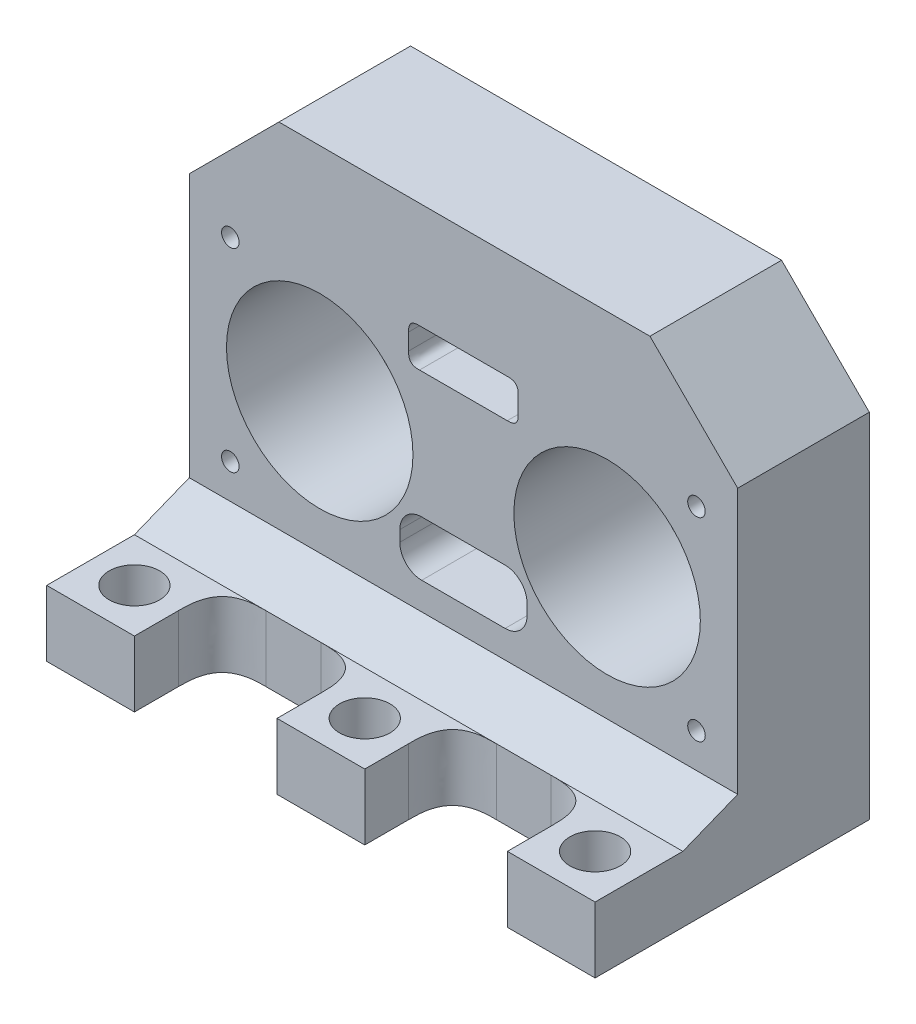
SolidWorks part; units mm, degrees
ref_plane "Plan de face" through (0, 0, 0) normal (0, 0, 1) x (1, 0, 0)
ref_plane "Plan de dessus" through (0, 0, 0) normal (0, 1, 0) x (1, 0, 0)
ref_plane "Plan de droite" through (0, 0, 0) normal (1, 0, 0) x (0, 0, -1)
sketch "Esquisse1" plane through (0, 0, 0) normal (0, 0, 1) x (1, 0, 0)
  line L0 (0, 0) -> (13.1, 0) construction
  line L1 (0, 0) -> (-13.1, 0) construction
  line L2 (0, 0) -> (0, -4.5) construction
  line L14 (0, -4.5) -> (0, -7) construction
  line L15 (0, -7) -> (5.8, -7) construction
  line L16 (5.8, -7) -> (5.8, -4.5)
  line L19 (5.8, -4.5) -> (-5.8, -4.5)
  line L20 (-5.8, -4.5) -> (-5.8, -9.5)
  line L27 (0, 0) -> (-24.9927, 0) construction
  line L28 (-5.8, -9.5) -> (5.8, -9.5)
  line L30 (-24.9927, 12) -> (-16.8203, 20.1724)
  line L31 (-24.9927, 12) -> (-24.9927, 20) construction
  line L32 (25.0073, -20) -> (0.0073, -20)
  line L33 (0.0073, -20) -> (-24.9927, -20)
  line L34 (-24.9927, -20) -> (-24.9927, 0)
  line L35 (25.0073, 20.1724) -> (25.0073, 12.1724) construction
  line L36 (5.8, -9.5) -> (5.8, -7)
  line L37 (-24.9927, 0) -> (-24.9927, 12)
  line L38 (25.0073, 12.1724) -> (25.0073, -20)
  line L39 (25.0073, 20.1724) -> (17.0073, 20.1724) construction
  line L40 (17.0073, 20.1724) -> (25.0073, 12.1724)
  line L41 (-24.9927, 20) -> (-16.8203, 20.1724) construction
  line L44 (-16.8203, 20.1724) -> (17.0073, 20.1724)
  circle A0 centre (-13.1, 0) radius 8.5
  circle A1 centre (13.1, 0) radius 8.5
  dimension "D3" = 5.8
  dimension "D4" = 4.5
  dimension "D2" = 13.1
  dimension "D5" = 2.5
  dimension "D6" = 11.6
  dimension "D7" = 7
  dimension "D8" = 5
  dimension "D11" = 8
  dimension "D12" = 20
  dimension "D13" = 25
  dimension "D14" = 25
  dimension "D16" = 40
  dimension "D17" = 40.1724
extrude "Boss.-Extru.1" add sketch "Esquisse1" along normal blind 12 contours L44 L30 L37 L34 L33 L32 L38 L40 L20 A1 A0 region at (0.0304, -0.3939, 0)
fillet "Congé1" radius 2 4 edges at (5.8, -9.5, 6) (-5.8, -9.5, 6) (5.8, -4.5, 6) (-5.8, -4.5, 6)
sketch "Esquisse2" plane through (0, 0, 0) normal (0, 0, -1) x (-1, 0, 0)
  line L4 (-5.8, -6.5) -> (-3.8, -6.5) construction
  line L5 (-3.8, -6.5) -> (3.8, -6.5) construction
  line L6 (3.8, -6.5) -> (5.8, -6.5) construction
  line L7 (5.8, -6.5) -> (5.8, -7.5) construction
  line L8 (-5.8, -7.5) -> (5.8, -7.5) construction
  line L9 (-5.8, -6.5) -> (-5.8, -7.5)
  line L10 (5.8, -6.5) -> (5.8, -7.5)
  line L12 (-3.8, -4.5) -> (-3.8, -9.5)
  line L13 (-3.8, -9.5) -> (3.8, -9.5)
  line L14 (3.8, -4.5) -> (3.8, -9.5)
  line L15 (-3.8, -4.5) -> (3.8, -4.5)
  arc A1 (-5.8, -7.5) -> (-3.8, -9.5) centre (-3.8, -7.5) ccw construction
  arc A2 (3.8, -9.5) -> (5.8, -7.5) centre (3.8, -7.5) ccw construction
  arc A3 (-5.8, -6.5) -> (-3.8, -4.5) centre (-3.8, -6.5) cw
  arc A4 (-5.8, -7.5) -> (-3.8, -9.5) centre (-3.8, -7.5) ccw
  arc A5 (3.8, -9.5) -> (5.8, -7.5) centre (3.8, -7.5) ccw
  arc A6 (3.8, -4.5) -> (5.8, -6.5) centre (3.8, -6.5) cw
  arc A7 (5.8, -6.5) -> (3.8, -4.5) centre (3.8, -6.5) ccw construction
  line M11 (3.8, -9.5) -> (-3.8, -9.5)
  arc M12 (-3.8, -9.5) -> (-5.8, -7.5) centre (-3.8, -7.5) cw
  line M13 (-5.8, -7.5) -> (-5.8, -6.5)
  arc M14 (-5.8, -6.5) -> (-3.8, -4.5) centre (-3.8, -6.5) cw
  line M15 (-3.8, -4.5) -> (3.8, -4.5)
  arc M16 (3.8, -4.5) -> (5.8, -6.5) centre (3.8, -6.5) cw
  line M17 (5.8, -6.5) -> (5.8, -7.5)
  arc M18 (5.8, -7.5) -> (3.8, -9.5) centre (3.8, -7.5) cw
extrude "Boss.-Extru.2" add sketch "Esquisse2" against normal blind 6 contours L12 M14 M13 M12 | L14 L12 M15 M11 | L14 M16 M18 M17 region at (4.6853, -7, 0) region at (0, -7, 0) region at (-4.6853, -7, 0)
sketch "Esquisse3" plane through (0, 0, 12) normal (0, 0, 1) x (1, 0, 0)
  line L1 (0, 10.1) -> (22.75, 10.1) construction
  line L2 (0, 10.1) -> (-22.75, 10.1) construction
  line L3 (-22.75, 10.1) -> (-22.75, 8.85) construction
  line L4 (22.75, 10.1) -> (22.75, 8.85) construction
  line L5 (55, 0) -> (-55, 0) construction
  line L10 (-22.75, 8.85) -> (-21.25, 8.85) construction
  line L11 (22.75, 8.85) -> (21.25, 8.85) construction
  circle A5 centre (-21.25, 8.85) radius 0.8
  circle A6 centre (21.25, 8.85) radius 0.8
  point P16 (0, 0)
  dimension "D2" = 22.75
  dimension "D7" = 1.5
  dimension "D1" = 10.1
  dimension "D3" = 10.1
  dimension "D4" = 22.75
  dimension "D5" = 1.25
  dimension "D6" = 1.25
  dimension "D8" = 1.5
extrude "Enlèv. mat.-Extru.1" cut sketch "Esquisse3" against normal blind 5
mirror "Symétrie1" about plane through (0, 0, 0) normal (0, 1, 0) of "Enlèv. mat.-Extru.1"
sketch "Esquisse5" plane through (0, 0, 12) normal (0, 0, 1) x (1, 0, 0)
  line L0 (0, 0) -> (0, 7)
  line L1 (0, 7) -> (0, 10.5)
  line L2 (0, 10.5) -> (5, 10.5)
  line L3 (5, 10.5) -> (5, 7)
  line L4 (5, 7) -> (-5, 7)
  line L5 (-5, 7) -> (-5, 10.5)
  line L6 (-5, 10.5) -> (0, 10.5)
  dimension "D1" = 7
  dimension "D2" = 3.5
  dimension "D3" = 10
extrude "Enlèv. mat.-Extru.2" cut sketch "Esquisse5" against normal blind 6 contours L2 L3 L4 L5 L6
fillet "Congé2" radius 1 4 edges at (5, 7, 9) (5, 10.5, 9) (-5, 10.5, 9) (-5, 7, 9) curvature continuous yes
sketch "Esquisse7" plane through (0, -20, 0) normal (0, -1, 0) x (1, 0, 0)
  line L0 (-24.9927, 0) -> (-24.9927, 5) construction
  line L1 (-24.9927, 12) -> (-24.9927, 0) construction
  line L3 (-24.9927, 17) -> (-24.9927, 25)
  line L4 (-24.9927, 25) -> (-16.9927, 25)
  line L5 (-16.9927, 25) -> (-16.9927, 17)
  line L7 (-16.9927, 17) -> (-24.9927, 17)
  line L8 (-24.9927, 17) -> (-16.9927, 25) construction
  line L14 (25.0073, 0) -> (25.0073, 12) construction
  line L16 (25.0073, 12) -> (25.0073, 17) construction
  line L17 (25.0073, 17) -> (25.0073, 25)
  line L22 (-24.9927, 17) -> (-20.9927, 17) construction
  line L23 (-20.9927, 17) -> (-20.9927, 21) construction
  line L24 (-20.9927, 17) -> (-16.9927, 17) construction
  line L25 (25.0073, 17) -> (17.0073, 17)
  line L26 (17.0073, 17) -> (17.0073, 25)
  line L27 (17.0073, 25) -> (25.0073, 25)
  line L28 (25.0073, 17) -> (17.0073, 25) construction
  circle A3 centre (-20.9927, 21) radius 2.3
  circle A5 centre (21.0073, 21) radius 2.3
  dimension "D1" = 5
  dimension "D3" = 5
  dimension "D2" = 12
  dimension "D4" = 8
extrude "Boss.-Extru.4" add sketch "Esquisse7" against normal blind 6 contours L7 L5 L4 L3 A3 | L27 L26 L25 L17 A5 region at (-24.8795, -20, 21) region at (21.0073, -20, 17.1131)
sketch "Esquisse12" plane through (25.0073, 0, 0) normal (1, 0, 0) x (0, 0, -1)
  line L0 (-17, -20) -> (-12, -20)
  line L1 (-12, -20) -> (-12, -12)
  line L2 (-12, 12.1724) -> (-12, -20) construction
  line L3 (-17, -14) -> (-17, -20)
  line L4 (-17, -14) -> (-12, -12)
extrude "Boss.-Extru.6" add sketch "Esquisse12" against normal blind 50
sketch "Esquisse15" plane through (0, -20, 0) normal (0, -1, 0) x (1, 0, 0)
  line L0 (0.0073, 17) -> (0.0073, 21) construction
  line L1 (-16.9927, 17) -> (17.0073, 17) construction
  line L2 (0.0073, 17) -> (4.0073, 17)
  line L3 (4.0073, 17) -> (4.0073, 25)
  line L4 (4.0073, 25) -> (-3.9927, 25)
  line L5 (-3.9927, 25) -> (-3.9927, 17)
  line L6 (-3.9927, 17) -> (0.0073, 17)
  circle A0 centre (0.0073, 21) radius 2.3
extrude "Boss.-Extru.7" add sketch "Esquisse15" against normal blind 6
fillet "Congé3" radius 4 4 edges at (17.0073, -17, 17) (4.0073, -17, 17) (-3.9927, -17, 17) (-16.9927, -17, 17) curvature continuous yes
